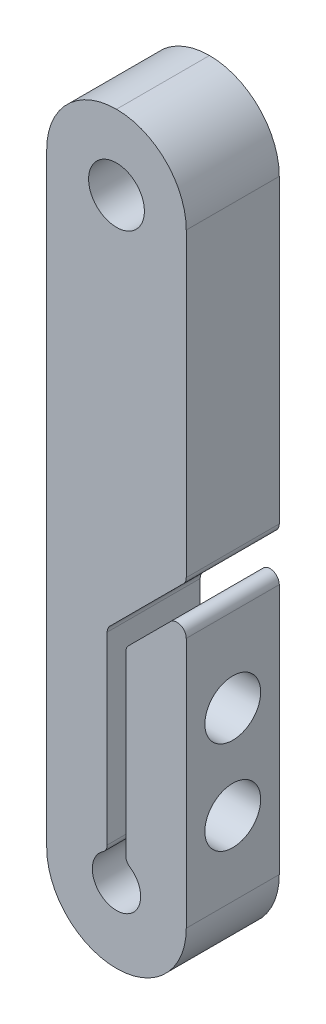
SolidWorks part; units mm, degrees
ref_plane "Front" through (0, 0, 0) normal (0, 0, 1) x (1, 0, 0)
ref_plane "Top" through (0, 0, 0) normal (0, 1, 0) x (1, 0, 0)
ref_plane "Right" through (0, 0, 0) normal (1, 0, 0) x (0, 0, -1)
sketch "Esquisse1" plane through (0, 0, 0) normal (0, 0, 1) x (1, 0, 0)
  line L1 (0, 0) -> (15, 0)
  line L2 (0, 0) -> (0, 80)
  line L3 (0, 80) -> (15, 80)
  line L4 (15, 0) -> (15, 80)
  dimension "D1" = 15
  dimension "D2" = 80
extrude "Boss.-Extru.1" add sketch "Esquisse1" along normal blind 10
sketch "Esquisse2" plane through (0, 0, 10) normal (0, 0, 1) x (1, 0, 0)
  line L0 (7.5, 80) -> (7.5, 81) construction
  line L1 (15, 80) -> (0, 80) construction
  line L2 (0, 0) -> (15, 0) construction
  line L3 (7.5, 8) -> (7.5, 0) construction
  circle A1 centre (7.5, 72) radius 3
  circle A2 centre (7.5, 8) radius 2.6
  point P11 (7.5, 0)
  dimension "D2" = 8
  dimension "D3" = 6
  dimension "D4" = 5.2
  dimension "D5" = 8
extrude "Enlèv. mat.-Extru.1" cut sketch "Esquisse2" against normal up to vertex (10 mm away) up to point (0, 80, 0)
fillet "Congé1" radius 7.5 4 edges at (15, 80, 5) (0, 80, 5) (15, 0, 5) (0, 0, 5)
sketch "Esquisse3" plane through (0, 0, 10) normal (0, 0, 1) x (1, 0, 0)
  line L0 (6.5, 10.4) -> (6.5, 31.2284)
  line L1 (6.5, 31.2284) -> (15, 39.7284)
  line L2 (15, 7.5) -> (15, 72.5) construction
  line L3 (15, 39.7284) -> (15, 36.9)
  line L4 (15, 36.9) -> (8.5, 30.4)
  line L5 (8.5, 30.4) -> (8.5, 10.4)
  line L6 (8.5, 10.4) -> (6.5, 10.4)
  line L7 (7.5, 10.6) -> (7.5, 10.4) construction
  circle A0 centre (7.5, 8) radius 2.6 construction
  dimension "D1" = 2
  dimension "D2" = 2
  dimension "D3" = 20
  dimension "D4" = 135
extrude "Enlèv. mat.-Extru.2" cut sketch "Esquisse3" against normal through all
sketch "Esquisse4" plane through (15, 0, 0) normal (1, 0, 0) x (0, 0, -1)
  line L0 (-5, 7.5) -> (-5, 36.9) construction
  line L1 (-10, 7.5) -> (0, 7.5) construction
  line L2 (0, 36.9) -> (-10, 36.9) construction
  circle A0 centre (-5, 15.5) radius 2.1
  circle A1 centre (-5, 25.5) radius 2.1
  dimension "D1" = 10
  dimension "D2" = 4.2
  dimension "D3" = 8
extrude "Enlèv. mat.-Extru.3" cut sketch "Esquisse4" against normal through all
sketch "Esquisse5" plane through (15, 0, 0) normal (1, 0, 0) x (0, 0, -1)
  circle A0 centre (-5, 25.5) radius 3
  circle A1 centre (-5, 15.5) radius 3
  dimension "D1" = 6
extrude "Enlèv. mat.-Extru.4" cut sketch "Esquisse5" against normal up to vertex (6.5 mm away) up to point (8.5, 30.4, 0)
fillet "Congé2" radius 1 6 edges at (15, 36.9, 5) (8.5, 10.4, 5) (6.5, 10.4, 5) (8.5, 30.4, 5) (15, 39.7284, 5) (6.5, 31.2284, 5)
